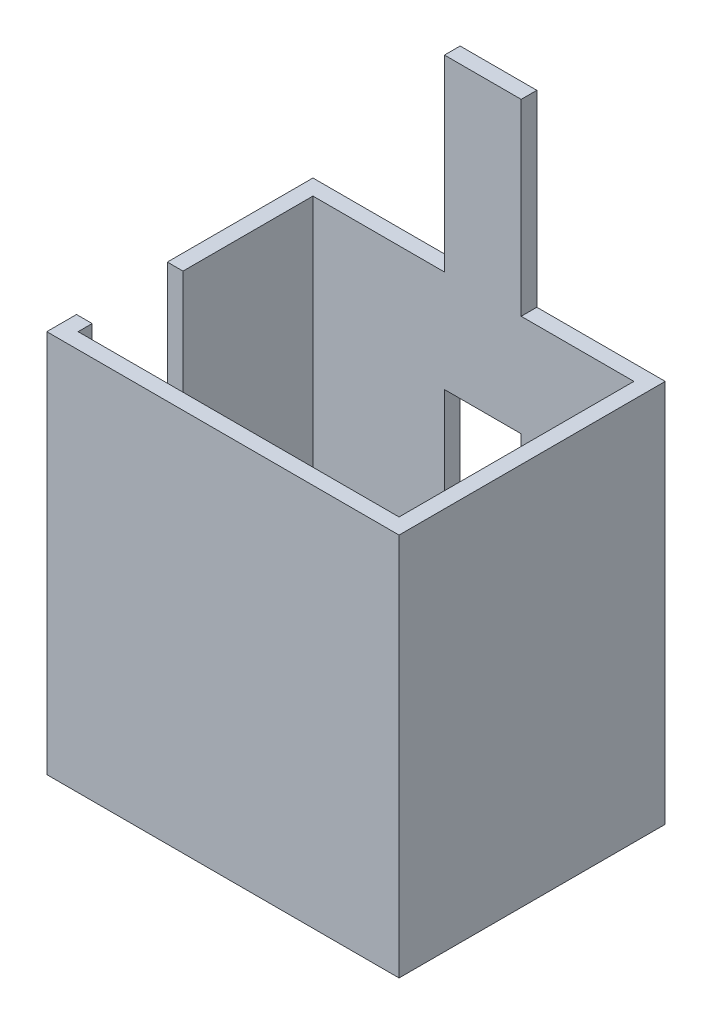
SolidWorks part; units mm, degrees
ref_plane "Front Plane" through (0, 0, 0) normal (0, 0, 1) x (1, 0, 0)
ref_plane "Top Plane" through (0, 0, 0) normal (0, 1, 0) x (1, 0, 0)
ref_plane "Right Plane" through (0, 0, 0) normal (1, 0, 0) x (0, 0, -1)
sketch "Sketch1" plane through (0, 0, 0) normal (0, 1, 0) x (1, 0, 0)
  line L0 (1360, 1500) -> (1360, 0)
  line L1 (0, 0) -> (2050, 0)
  line L2 (0, 0) -> (0, 1500)
  line L3 (0, 1500) -> (2050, 1500)
  line L4 (2050, 0) -> (2050, 1500)
  line L5 (-100, 1600) -> (2150, 1600)
  line L6 (0, 1500) -> (780, 1500)
  line L7 (0, 1500) -> (0, 1030)
  line L8 (0, 1030) -> (780, 1030)
  line L9 (780, 1500) -> (780, 1030)
  line L10 (2150, -100) -> (2150, 1600)
  line L11 (-100, -100) -> (2150, -100)
  line L12 (-100, -100) -> (-100, 1600)
  line L13 (0, 90) -> (-100, 90)
  line L14 (0, 670) -> (-100, 670)
  line L15 (560, 0) -> (560, -50)
  line L16 (560, -50) -> (1160, -50)
  line L17 (1160, -50) -> (1160, 0)
  line L18 (860, -50) -> (860, 0)
  line L19 (840, 1500) -> (840, 1600)
  line L20 (1330, 1600) -> (1330, 1500)
  line L22 (910, 1450) -> (1310, 1450)
  line L23 (910, 1450) -> (910, 1250)
  line L24 (910, 1250) -> (1310, 1250)
  line L25 (1310, 1450) -> (1310, 1250)
  ellipse E0 centre (1110, 1050) end of major axis (1110, 850) minor radius 160
  point P33 (1272.329, 1348.5704)
  point P39 (910, 1407.2851)
  point P40 (0, 0)
  point P41 (1274.275, 1050)
  point P42 (0, 0)
  dimension "D1" = 2050
  dimension "D2" = 1500
  dimension "D4" = 830
  dimension "D5" = 90
  dimension "D6" = 690
  dimension "D7" = 780
  dimension "D8" = 470
  dimension "D9" = 600
  dimension "D10" = 200
  dimension "D11" = 720
  dimension "D12" = 490
  dimension "D13" = 250
  dimension "D14" = 650
  dimension "D15" = 400
  dimension "D16" = 200
  dimension "D17" = 50
  dimension "D18" = 320
  dimension "D19" = 50
  dimension "D3" = 100
extrude "Boss-Extrude2" add sketch "Sketch1" along normal blind 2450 contours L3 L19 L5 L12 L14 L2 | L5 L20 L3 L4 L1 L17 L16 L15 L2 L13 L12 L11 L10 | L18 L16 L17 L1 | L16 L18 L1 L15 | L20 L5 L19 L3 region at (1345, 0, -1528.2002) region at (1085, 0, -1550) region at (1010, 0, 25) region at (810, 0, -1513.2231) region at (710, 0, 25)
extrude "Boss-Extrude3" add sketch "Sketch1<5>" along normal blind 2450 from offset 1200 contours L20 L5 L19 L3 region at (1085, 0, -1550)
sketch "Sketch1<5>" plane through (0, 0, 0) normal (0, 1, 0) x (1, 0, 0) same geometry as "Sketch1"
extrude "Cut-Extrude1" cut sketch "Sketch1<6>" along direction (0, 1, 0) on the side of the normal offset from surface (1800 mm away) 650 contours L20 L5 L19 L3 region at (1085, 0, -1550) up to face at (246.6667, 2450, -1256.6667)
sketch "Sketch1<6>" plane through (0, 0, 0) normal (0, 1, 0) x (1, 0, 0) same geometry as "Sketch1"
